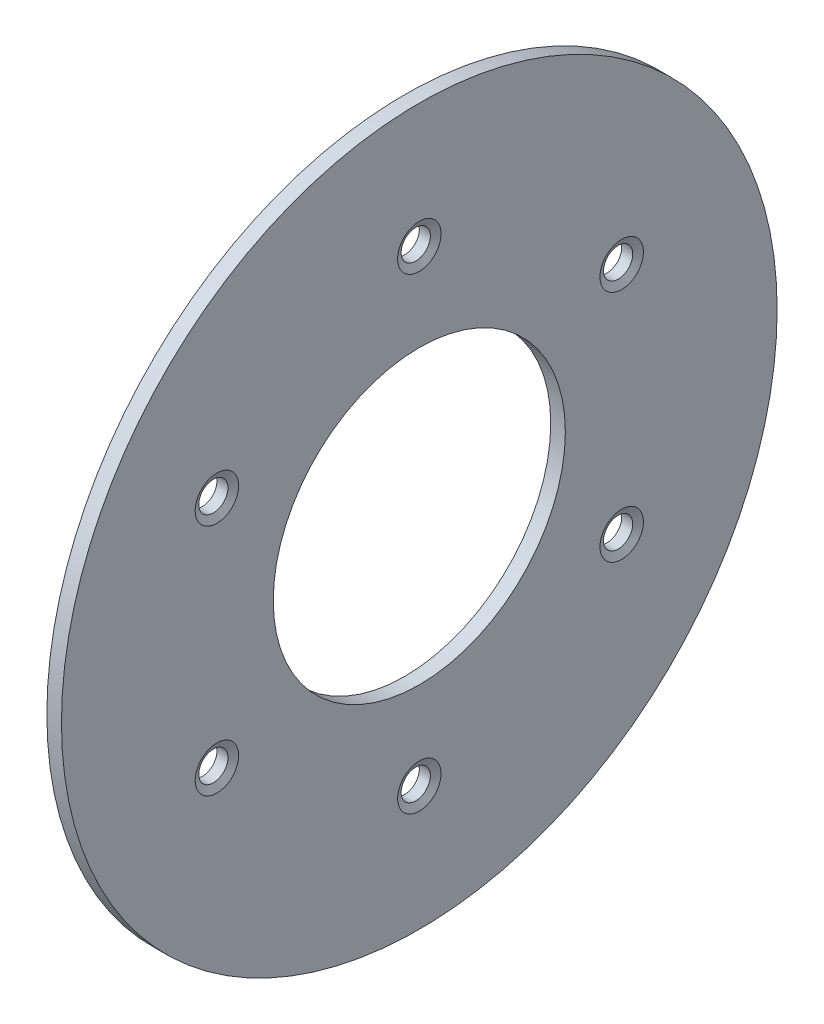
SolidWorks part; units mm, degrees
material "AISI 1020 Steel, Cold Rolled"
ref_plane "Front Plane" through (0, 0, 0) normal (1, 0, 0) x (0, 1, 0)
ref_plane "Top Plane" through (0, 0, 0) normal (0, 0, 1) x (0, 1, 0)
ref_plane "Right Plane" through (0, 0, 0) normal (0, 1, 0) x (-1, 0, 0)
sketch "Sketch1" plane through (0, 0, 0) normal (1, 0, 0) x (0, 1, 0)
  line L0 (0, 59.2655) -> (0, -55.9487) construction
  line L1 (-63.6867, 0) -> (59.9067, 0) construction
  circle A0 centre (0, 0) radius 49
  circle A1 centre (0, 0) radius 20
  circle A2 centre (32, 0) radius 2
  dimension "D1" = 98
  dimension "D2" = 40
  dimension "D4" = 4
  dimension "D3" = 32
extrude "Boss-Extrude1" add sketch "Sketch1" along normal blind 2 contours A0 | A1
extrude "Cut-Extrude2" cut sketch "Sketch1<3>" along normal blind 0.5 contours A2
sketch "Sketch1<3>" plane through (0, 0, 0) normal (1, 0, 0) x (0, 1, 0) same geometry as "Sketch1"
extrude "Cut-Extrude3" cut sketch "Sketch1<4>" along normal through all contours A2
sketch "Sketch1<4>" plane through (0, 0, 0) normal (1, 0, 0) x (0, 1, 0) same geometry as "Sketch1"
pattern_circular "CirPattern1" count 6 over 360 about axis through (0, 0, 0) along (1, 0, 0) of "Cut-Extrude3", "Cut-Extrude2"
ref_axis "Axis1" through (13.4506, 0, 0) along (1, 0, 0)
ref_axis "Axis2" through (13.362, 16, 27.7128) along (-1, 0, 0)
ref_plane "Plane1" through (0, 16, 0) normal (0, 1, 0) x (-1, 0, 0)
sketch "Sketch3" plane through (0, 16, 0) normal (0, 1, 0) x (-1, 0, 0)
  line L0 (-15.1346, 27.7128) -> (2.1015, 27.7128)
  line L1 (-13.362, 27.7128) -> (1, 27.7128) construction
  line L3 (-2.4993, 31.6858) -> (-1.5, 29.6859)
  line L4 (-1.5, 29.6859) -> (-1.5, 25.7398)
  line L5 (-2, 49) -> (-2, -49) construction
  line L6 (-2.4993, 23.7398) -> (-1.5, 25.7398)
  line L7 (-2.4993, 31.6858) -> (-2.4993, 23.7398)
  point P10 (-1.5, 27.7128)
  dimension "D1" = 0.5
  dimension "D2" = 126.9
revolve "Cut-Revolve1" cut sketch "Sketch3" angle 360 about L0 region at (2.0557, 16, 29.2554)
pattern_circular "CirPattern2" count 6 over 360 about axis through (2, 0, 0) along (1, 0, 0) of "Cut-Revolve1"
